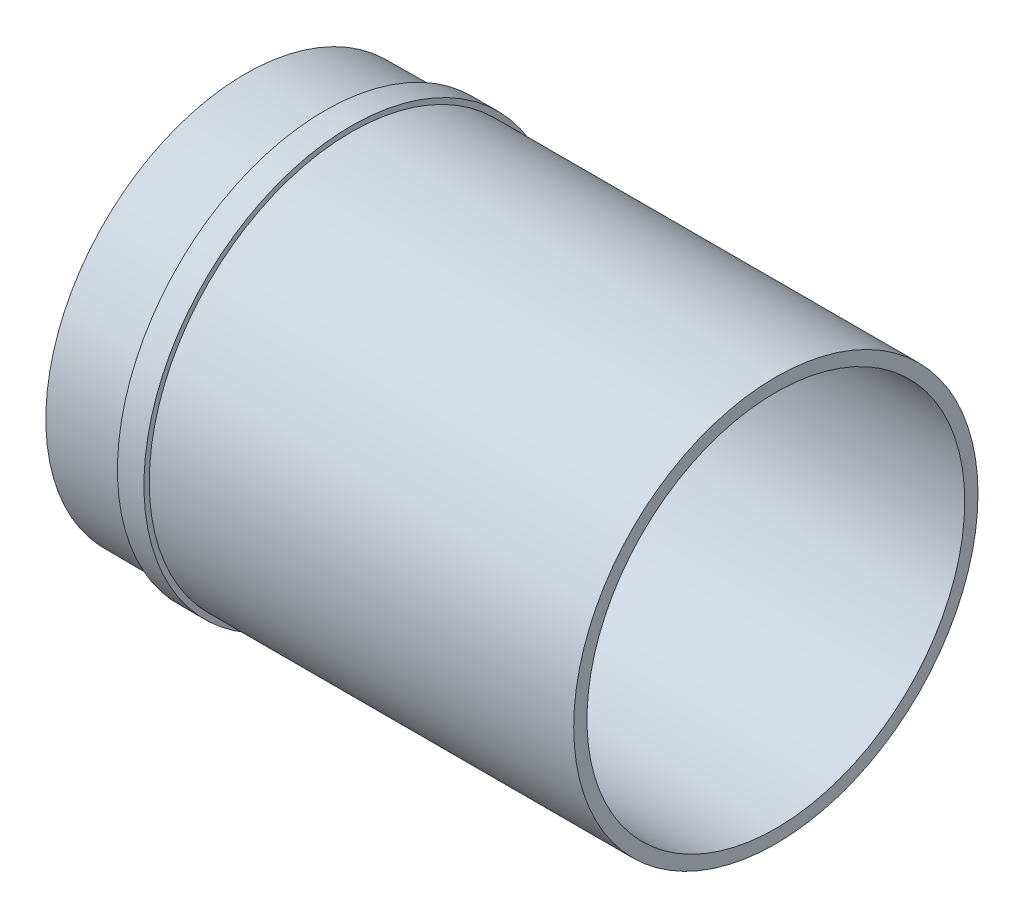
SolidWorks part; units mm, degrees
material "Thornel VCB-20 Carbon Cloth"
ref_plane "Front Plane" through (0, 0, 0) normal (0, 0, 1) x (1, 0, 0)
ref_plane "Top Plane" through (0, 0, 0) normal (0, 1, 0) x (1, 0, 0)
ref_plane "Right Plane" through (0, 0, 0) normal (1, 0, 0) x (0, 0, -1)
sketch "Sketch1" plane through (0, 0, 0) normal (0, 0, 1) x (1, 0, 0)
  line L0 (0, 0) -> (0, 3483.1) construction
  line L1 (0, 3635.5) -> (0, 3633.5)
  line L2 (0, 3557.2968) -> (-750, 3557.2968) construction
  line L3 (0, 3633.5) -> (0, 3635.5) construction
  line L4 (0, 3633.5) -> (160, 3633.5)
  line L5 (-5, 3628.5) -> (160, 3628.5)
  line L6 (-5, 3630.4966) -> (-5, 3628.5)
  line L7 (-750, 3557.2968) -> (-725.3758, 3557.2968)
  line L8 (160, 3633.5) -> (160, 3628.5)
  line L9 (-650, 3576.9205) -> (-650, 3571.8385)
  line L10 (-650, 3571.8385) -> (-600, 3571.8385)
  line L11 (-600, 3571.8385) -> (-600, 3580.5768)
  line L12 (-2.5, 3631) -> (157.5, 3631) construction
  line L13 (-2.5, 3631) -> (157.5, 3631) construction
  line L14 (-725.628, 3559.7968) -> (-725.628, 3559.7968)
  line L15 (-500, 3598.4287) -> (-500, 3595.9046)
  line L18 (157.5, 3631) -> (157.5, 3631)
  line L21 (-2.5, 3632.9991) -> (-2.5, 3631) construction
  line L22 (-2.5, 3632.9991) -> (-2.5, 3631) construction
  line L23 (-470, 3604.991) -> (-470, 3602.4698)
  line L24 (-320, 3621.3893) -> (-320, 3618.8795)
  line L25 (-350, 3616.1014) -> (-350, 3613.5897)
  line L26 (-40, 3632.7798) -> (-40, 3630.2796)
  line L27 (-10, 3632.9862) -> (-10, 3635.4862)
  line L28 (-170, 3629.0204) -> (-170, 3631.5231)
  line L29 (-200, 3627.4907) -> (-200, 3624.9869)
  line L30 (-40, 3630.2796) -> (-40, 3628.5)
  line L31 (-40, 3628.5) -> (-5, 3628.5)
  line L32 (-10, 3632.9862) -> (-10, 3632.6862)
  line L33 (-170, 3629.0204) -> (-170, 3628.7201)
  line L34 (-320, 3618.8795) -> (-320, 3618.5784)
  line L35 (-470, 3602.4698) -> (-470, 3602.1673)
  arc A0 (0, 3635.5) -> (-750, 3557.2968) centre (0, 0) ccw
  arc A1 (-5, 3630.4966) -> (-600, 3580.5768) centre (0, 0) ccw
  arc A2 (-5, 3630.4966) -> (-748.9685, 3552.4043) centre (0, 0) ccw construction
  arc A5 (-650, 3571.8385) -> (-725.3758, 3557.2968) centre (0, 0) ccw
  arc A6 (-5, 3630.4966) -> (-725.3758, 3557.2968) centre (0, 0) ccw construction
  arc A7 (-2.5, 3632.9991) -> (-725.628, 3559.7968) centre (0, 0) ccw construction
  arc A8 (-2.5, 3632.9991) -> (-725.628, 3559.7968) centre (0, 0) ccw construction
  arc A9 (-500, 3598.4287) -> (-470, 3602.4698) centre (0, 0) cw
  arc A10 (-350, 3616.1014) -> (-320, 3618.8795) centre (0, 0) cw
  arc A11 (-10, 3632.9862) -> (-40, 3632.7798) centre (0, 0) ccw
  arc A12 (-170, 3629.0204) -> (-200, 3627.4907) centre (0, 0) ccw
  arc A13 (-40, 3632.4798) -> (-10, 3632.6862) centre (0, 0) cw
  arc A14 (-200, 3627.1903) -> (-170, 3628.7201) centre (0, 0) cw
  arc A15 (-350, 3615.8) -> (-320, 3618.5784) centre (0, 0) cw
  arc A16 (-500, 3598.1258) -> (-470, 3602.1673) centre (0, 0) cw
  dimension "D1" = 7271
  dimension "D7" = 100
  dimension "D10" = 30
  dimension "D8" = 3633
  dimension "D12" = 3633
  dimension "D15" = 3633
  dimension "D18" = 3633
  dimension "D21" = 3632.7
  dimension "D23" = 3632.7
  dimension "D22" = 3632.7
  dimension "D24" = 3632.7
  dimension "D2" = 152.4
  dimension "D3" = 750
  dimension "D4" = 2
  dimension "D5" = 160
  dimension "D9" = 50
  dimension "D11" = 180
  dimension "D13" = 30
  dimension "D14" = 180
  dimension "D16" = 30
  dimension "D17" = 200
  dimension "D19" = 30
  dimension "D20" = 180
  dimension "D6" = 5
revolve "Revolve1" add sketch "Sketch1" angle 360 about L2 region at (67.0359, 3631.1274, 0) region at (-22.1698, 3629.4592, 0)
